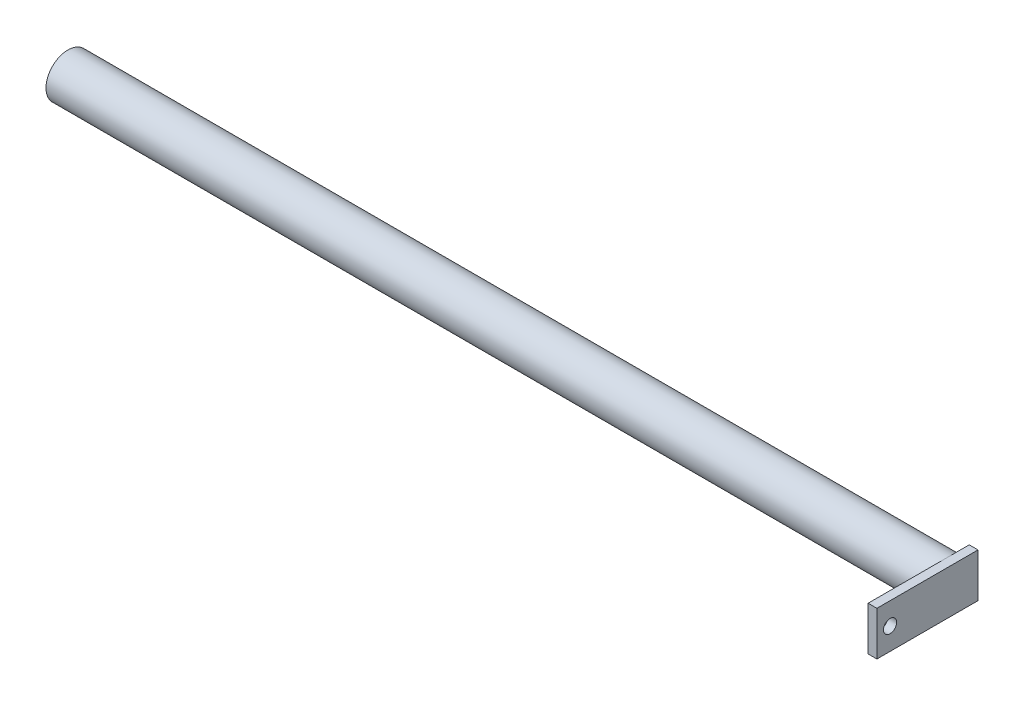
SolidWorks part; units mm, degrees
ref_plane "Front Plane" through (0, 0, 0) normal (1, 0, 0) x (0, 1, 0)
ref_plane "Top Plane" through (0, 0, 0) normal (0, 0, 1) x (0, 1, 0)
ref_plane "Right Plane" through (0, 0, 0) normal (0, 1, 0) x (-1, 0, 0)
sketch "Sketch2" plane through (0, 0, 0) normal (0, 1, 0) x (-1, 0, 0)
  line L0 (0, 0) -> (-90.3007, 0) construction
  line L1 (-200, -8) -> (200, -8)
  line L2 (-200, -8) -> (-200, -10)
  line L3 (-200, -10) -> (200, -10)
  line L4 (200, -8) -> (200, -10)
  point P5 (0, -8)
  dimension "D1" = 400
  dimension "D2" = 2
  dimension "D3" = 8
revolve "Revolve1" add sketch "Sketch2" angle 360 about L0
sketch "Sketch3" plane through (200, 0, 0) normal (1, 0, 0) x (0, 1, 0)
  line L1 (-10, -10) -> (10, -10)
  line L2 (-10, -10) -> (-10, 36)
  line L3 (-10, 36) -> (10, 36)
  line L4 (10, -10) -> (10, 36)
  circle A0 centre (0, 0) radius 10 construction
  circle A1 centre (0, 30) radius 3
  point P6 (0, -10)
  point P8 (0, 0)
  point P11 (0, 36)
  dimension "D1" = 30
  dimension "D2" = 6
  dimension "D3" = 6
extrude "Boss-Extrude1" add sketch "Sketch3" along normal blind 4
